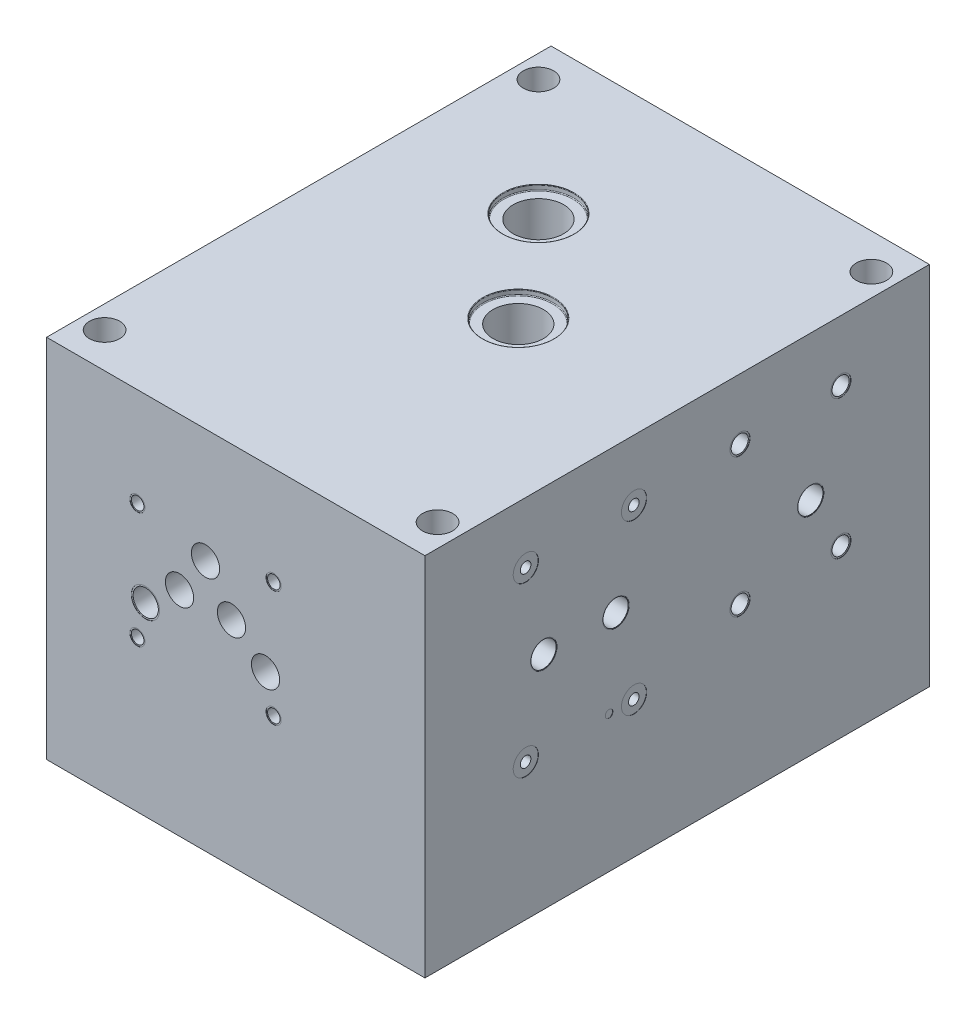
SolidWorks part; units mm, degrees
ref_plane "前视基准面" through (0, 0, 0) normal (0, 0, 1) x (1, 0, 0)
ref_plane "上视基准面" through (0, 0, 0) normal (0, 1, 0) x (1, 0, 0)
ref_plane "右视基准面" through (0, 0, 0) normal (1, 0, 0) x (0, 0, -1)
sketch "草图1" plane through (0, 0, 0) normal (0, 1, 0) x (1, 0, 0)
  line L1 (-75, -100) -> (75, -100)
  line L2 (-75, -100) -> (-75, 100)
  line L3 (-75, 100) -> (75, 100)
  line L4 (75, -100) -> (75, 100)
  line L5 (-75, -100) -> (75, 100) construction
  line L6 (-75, 100) -> (75, -100) construction
  point P0 (0, 0)
  dimension "D1" = 150
  dimension "D2" = 200
extrude "凸台-拉伸1" add sketch "草图1" along normal blind 145
sketch "草图2" plane through (0, 145, 0) normal (0, 1, 0) x (1, 0, 0)
  line L2 (-75, -100) -> (75, -100) construction
  line L3 (-75, 100) -> (-75, -100) construction
  line L4 (75, -100) -> (75, 100) construction
  circle A0 centre (12, 0) radius 10
  circle A1 centre (-20, 40) radius 10
  dimension "D1" = 20
  dimension "D4" = 20
  dimension "D2" = 100
  dimension "D3" = 87
  dimension "D5" = 95
  dimension "D6" = 140
extrude "切除-拉伸1" cut sketch "草图2" against normal through all
sketch "草图4" plane through (0, 0, 100) normal (0, 0, 1) x (1, 0, 0)
  line L0 (0, -7.783) -> (0, 155.8049) construction
  line L1 (-75, 0) -> (75, 0) construction
  line L2 (75, 145) -> (75, 0) construction
  circle A0 centre (15, 60) radius 3
  circle A1 centre (-39, 60) radius 3
  circle A2 centre (-39, 106) radius 3
  circle A3 centre (15, 106) radius 3
  circle A4 centre (-12, 99.7) radius 5.6
  circle A5 centre (-22.3, 84.6) radius 5.6
  circle A6 centre (-35.8, 73.5) radius 5.6
  circle A7 centre (-1.7, 84.6) radius 5.6
  circle A8 centre (11.8, 73.5) radius 5.6
  dimension "D1" = 6
  dimension "D4" = 6
  dimension "D2" = 6
  dimension "D3" = 6
  dimension "D10" = 11.2
  dimension "D13" = 11.2
  dimension "D16" = 11.2
  dimension "D19" = 11.2
  dimension "D22" = 11.2
  dimension "D5" = 54
  dimension "D6" = 46
  dimension "D7" = 54
  dimension "D8" = 60
  dimension "D9" = 60
  dimension "D11" = 27
  dimension "D12" = 6.3
  dimension "D14" = 21.4
  dimension "D15" = 16.7
  dimension "D17" = 3.2
  dimension "D18" = 32.5
  dimension "D20" = 21.4
  dimension "D21" = 37.3
  dimension "D23" = 50.8
  dimension "D24" = 32.5
extrude "切除-拉伸2" cut sketch "草图4" against normal blind 0.1
hole_wizard "M6 螺纹孔1" positions "3D草图1" profile "草图5" tap size "M6" standard "GB"
sketch3d "3D草图1"
  line L0 (-39, 106, 99.9) -> (-39, 106, 100) construction
  line L1 (-39, 60, 99.9) -> (-39, 60, 100) construction
  line L2 (15, 60, 99.9) -> (15, 60, 100) construction
  line L3 (15, 106, 99.9) -> (15, 106, 100) construction
  point P0 (-39, 106, 99.9)
  point P4 (-39, 60, 99.9)
  point P8 (15, 60, 99.9)
  point P12 (15, 106, 100)
sketch "草图5" plane through (-39, 106, 99.9) normal (1, 0, 0) x (0, -1, 0)
  line L0 (0, 0) -> (0, 16.5022)
  line L1 (0, 16.5022) -> (2.5, 15)
  line L2 (2.5, 15) -> (2.5, 0)
  line L5 (2.5, 0) -> (0, 0)
  line L10 (0, 16.5022) -> (-2.5, 15) construction
  line L11 (0, -6.35) -> (0, 107.95) construction
  dimension "螺纹孔钻头直径" = 5
  dimension "螺纹孔钻头深度" = 15
  dimension "导头角度" = 118
cosmetic thread "孔螺蚊线1" parameters "D1"=12, "D2"=6
cosmetic thread "孔螺蚊线2" parameters "D1"=12, "D2"=6
cosmetic thread "孔螺蚊线3" parameters "D1"=12, "D2"=6
cosmetic thread "孔螺蚊线4" parameters "D1"=12, "D2"=6
sketch "草图6" plane through (75, 0, 0) normal (1, 0, 0) x (0, 0, -1)
  line L0 (-100, 145) -> (-100, 0) construction
  line L2 (-100, 0) -> (100, 0) construction
  circle A0 centre (-60, 120.9) radius 5
  circle A1 centre (-17.1, 120.9) radius 5
  circle A2 centre (-60, 54.2) radius 5
  circle A3 centre (-17.1, 54.2) radius 5
  circle A4 centre (52.9, 87.6) radius 5.25
  circle A5 centre (-52.9, 87.6) radius 5.25
  circle A6 centre (-24.3, 87.6) radius 5.25
  circle A7 centre (-27, 54.2) radius 1.5
  circle A8 centre (24.9, 120.9) radius 4
  circle A9 centre (64.9, 120.9) radius 4
  circle A10 centre (24.9, 65.9) radius 4
  circle A11 centre (64.9, 65.9) radius 4
  dimension "D1" = 10
  dimension "D4" = 10
  dimension "D6" = 10
  dimension "D8" = 10
  dimension "D10" = 10.5
  dimension "D13" = 10.5
  dimension "D16" = 10.5
  dimension "D18" = 3
  dimension "D11" = 8
  dimension "D12" = 8
  dimension "D21" = 8
  dimension "D22" = 8
  dimension "D2" = 40
  dimension "D3" = 120.9
  dimension "D5" = 42.9
  dimension "D7" = 66.7
  dimension "D9" = 66.7
  dimension "D14" = 33.3
  dimension "D15" = 7.1
  dimension "D17" = 35.7
  dimension "D19" = 33
  dimension "D20" = 66.7
  dimension "D23" = 42
  dimension "D24" = 55
  dimension "D25" = 40
  dimension "D26" = 33.3
  dimension "D27" = 28
extrude "切除-拉伸3" cut sketch "草图6" against normal blind 0.1
hole_wizard "M5 螺纹孔2" positions "3D草图3" profile "草图8" tap size "M5" standard "GB"
sketch3d "3D草图3"
  line L0 (74.9, 120.9, 60) -> (75, 120.9, 60) construction
  line L1 (74.9, 120.9, 17.1) -> (75, 120.9, 17.1) construction
  line L2 (74.9, 54.2, 17.1) -> (75, 54.2, 17.1) construction
  line L3 (74.9, 54.2, 60) -> (75, 54.2, 60) construction
  point P0 (74.9, 120.9, 60)
  point P4 (74.9, 120.9, 17.1)
  point P8 (75, 54.2, 17.1)
  point P12 (74.9, 54.2, 60)
sketch "草图8" plane through (74.9, 120.9, 60) normal (0, 1, 0) x (0, 0, -1)
  line L0 (0, 0) -> (0, 13.6618)
  line L1 (0, 13.6618) -> (2.1, 12.4)
  line L2 (2.1, 12.4) -> (2.1, 0)
  line L5 (2.1, 0) -> (0, 0)
  line L10 (0, 13.6618) -> (-2.1, 12.4) construction
  line L11 (0, -6.35) -> (0, 107.95) construction
  dimension "螺纹孔钻头直径" = 4.2
  dimension "螺纹孔钻头深度" = 12.4
  dimension "导头角度" = 118
cosmetic thread "孔螺蚊线5" parameters "D1"=10, "D2"=5
cosmetic thread "孔螺蚊线6" parameters "D1"=10, "D2"=5
cosmetic thread "孔螺蚊线7" parameters "D1"=10, "D2"=5
cosmetic thread "孔螺蚊线8" parameters "D1"=10, "D2"=5
hole_wizard "Ø11.2 (11.2) 直径孔1" positions "3D草图4" profile "草图10" hole size "Ø11.2" standard "GB"
sketch3d "3D草图4"
  line L0 (-12, 99.7, 99.9) -> (-12, 99.7, 100) construction
  point P0 (-12, 99.7, 100)
sketch "草图10" plane through (-12, 99.7, 100) normal (1, 0, 0) x (0, -1, 0)
  line L0 (0, 0) -> (0, 83.3648)
  line L1 (0, 83.3648) -> (5.6, 80)
  line L2 (5.6, 80) -> (5.6, 0)
  line L5 (5.6, 0) -> (0, 0)
  line L10 (0, 83.3648) -> (-5.6, 80) construction
  line L11 (0, -6.35) -> (0, 107.95) construction
  dimension "孔直径" = 11.2
  dimension "孔深度" = 80
  dimension "导头角度" = 118
hole_wizard "Ø11.2 (11.2) 直径孔2" positions "3D草图5" profile "草图12" hole size "Ø11.2" standard "GB"
sketch3d "3D草图5"
  line L0 (11.8, 73.5, 99.9) -> (11.8, 73.5, 100) construction
  point P0 (11.8, 73.5, 99.9)
sketch "草图12" plane through (11.8, 73.5, 99.9) normal (1, 0, 0) x (0, -1, 0)
  line L0 (0, 0) -> (0, 58.3648)
  line L1 (0, 58.3648) -> (5.6, 55)
  line L2 (5.6, 55) -> (5.6, 0)
  line L5 (5.6, 0) -> (0, 0)
  line L10 (0, 58.3648) -> (-5.6, 55) construction
  line L11 (0, -6.35) -> (0, 107.95) construction
  dimension "孔直径" = 11.2
  dimension "孔深度" = 55
  dimension "导头角度" = 118
hole_wizard "Ø11.2 (11.2) 直径孔3" positions "3D草图7" profile "草图14" hole size "Ø11.2" standard "GB"
sketch3d "3D草图7"
  line L0 (-1.7, 84.6, 99.9) -> (-1.7, 84.6, 100) construction
  point P0 (-1.7, 84.6, 99.9)
sketch "草图14" plane through (-1.7, 84.6, 99.9) normal (1, 0, 0) x (0, -1, 0)
  line L0 (0, 0) -> (0, 58.3648)
  line L1 (0, 58.3648) -> (5.6, 55)
  line L2 (5.6, 55) -> (5.6, 0)
  line L5 (5.6, 0) -> (0, 0)
  line L10 (0, 58.3648) -> (-5.6, 55) construction
  line L11 (0, -6.35) -> (0, 107.95) construction
  dimension "孔直径" = 11.2
  dimension "孔深度" = 55
  dimension "导头角度" = 118
hole_wizard "Ø10.0 (10) 直径孔2" positions "3D草图10" profile "草图22" hole size "Ø10.0" standard "GB"
sketch3d "3D草图10"
  line L0 (-35.8, 73.5, 99.9) -> (-35.8, 73.5, 100) construction
  point P0 (-35.8, 73.5, 100)
sketch "草图22" plane through (-35.8, 73.5, 100) normal (1, 0, 0) x (0, -1, 0)
  line L0 (0, 0) -> (0, 143.0043)
  line L1 (0, 143.0043) -> (5, 140)
  line L2 (5, 140) -> (5, 0)
  line L5 (5, 0) -> (0, 0)
  line L10 (0, 143.0043) -> (-5, 140) construction
  line L11 (0, -6.35) -> (0, 107.95) construction
  dimension "孔直径" = 10
  dimension "孔深度" = 140
  dimension "导头角度" = 118
hole_wizard "Ø11.2 (11.2) 直径孔5" positions "3D草图11" profile "草图23" hole size "Ø11.2" standard "GB"
sketch3d "3D草图11"
  line L0 (-22.3, 84.6, 99.9) -> (-22.3, 84.6, 100) construction
  point P0 (-22.3, 84.6, 100)
sketch "草图23" plane through (-22.3, 84.6, 100) normal (1, 0, 0) x (0, -1, 0)
  line L0 (0, 0) -> (0, 58.3648)
  line L1 (0, 58.3648) -> (5.6, 55)
  line L2 (5.6, 55) -> (5.6, 0)
  line L5 (5.6, 0) -> (0, 0)
  line L10 (0, 58.3648) -> (-5.6, 55) construction
  line L11 (0, -6.35) -> (0, 107.95) construction
  dimension "孔直径" = 11.2
  dimension "孔深度" = 55
  dimension "导头角度" = 118
sketch "草图25" plane through (-75, 0, 0) normal (-1, 0, 0) x (0, 0, 1)
  line L0 (-100, 145) -> (100, 145) construction
  line L1 (100, 145) -> (100, 0) construction
  circle A0 centre (52, 89) radius 6
  dimension "D2" = 12
  dimension "D1" = 56
  dimension "D3" = 48
extrude "切除-拉伸13" cut sketch "草图25" against normal blind 0.1
cosmetic thread "装饰螺纹线10" parameters "D1"=6, "D2"=12.1
hole_wizard "Ø12.0 (12) 直径孔1" positions "3D草图12" profile "草图26" hole size "Ø12.0" standard "GB"
sketch3d "3D草图12"
  line L0 (-74.9, 89, 52) -> (-75, 89, 52) construction
  point P0 (-74.9, 89, 52)
sketch "草图26" plane through (-74.9, 89, 52) normal (0, 1, 0) x (0, 0, 1)
  line L0 (0, 0) -> (0, 55.6052)
  line L1 (0, 55.6052) -> (6, 52)
  line L2 (6, 52) -> (6, 0)
  line L5 (6, 0) -> (0, 0)
  line L10 (0, 55.6052) -> (-6, 52) construction
  line L11 (0, -6.35) -> (0, 107.95) construction
  dimension "孔直径" = 12
  dimension "孔深度" = 52
  dimension "导头角度" = 118
sketch "草图27" plane through (0, 0, -100) normal (0, 0, -1) x (-1, 0, 0)
  line L0 (-75, 145) -> (75, 145) construction
  line L1 (75, 145) -> (75, 0) construction
  circle A0 centre (40, 88) radius 13.5
  dimension "D2" = 27
  dimension "D1" = 57
  dimension "D3" = 35
extrude "切除-拉伸14" cut sketch "草图27" against normal blind 18
cosmetic thread "装饰螺纹线8" parameters "D1"=16, "D2"=27.1
sketch "草图31" plane through (0, 0, 0) normal (0, -1, 0) x (1, 0, 0)
  line L3 (-75, 100) -> (75, 100) construction
  line L4 (-75, -100) -> (-75, 100) construction
  circle A0 centre (-20, 19.3) radius 7
  dimension "D1" = 14
  dimension "D3" = 55
  dimension "D2" = 80.7
extrude "切除-拉伸16" cut sketch "草图31" against normal blind 1
sketch "草图34" plane through (-75, 0, 0) normal (-1, 0, 0) x (0, 0, 1)
  line L0 (100, 145) -> (100, 0) construction
  line L1 (-100, 145) -> (100, 145) construction
  circle A0 centre (52, 67.5) radius 6
  dimension "D3" = 12
  dimension "D1" = 48
  dimension "D2" = 77.5
extrude "切除-拉伸18" cut sketch "草图34" against normal blind 0.1
cosmetic thread "装饰螺纹线11" parameters "D1"=6, "D2"=12.1
hole_wizard "Ø14.75 (14.75) 直径孔1" positions "3D草图26" profile "草图60" hole size "Ø14.75" standard "GB"
sketch3d "3D草图26"
  line L0 (-20, 1, 19.3) -> (-20, 0, 19.3) construction
  point P0 (-20, 0, 19.3)
sketch "草图60" plane through (-20, 0, 19.3) normal (1, 0, 0) x (0, 0, -1)
  line L0 (0, 0) -> (0, 112.4313)
  line L1 (0, 112.4313) -> (7.375, 108)
  line L2 (7.375, 108) -> (7.375, 0)
  line L5 (7.375, 0) -> (0, 0)
  line L10 (0, 112.4313) -> (-7.375, 108) construction
  line L11 (0, -6.35) -> (0, 107.95) construction
  dimension "孔直径" = 14.75
  dimension "孔深度" = 108
  dimension "导头角度" = 118
hole_wizard "Ø12.0 (12) 直径孔2" positions "3D草图13" profile "草图35" hole size "Ø12.0" standard "GB"
sketch3d "3D草图13"
  line L0 (-74.9, 67.5, 52) -> (-75, 67.5, 52) construction
  point P0 (-75, 67.5, 52)
sketch "草图35" plane through (-75, 67.5, 52) normal (0, 1, 0) x (0, 0, 1)
  line L0 (0, 0) -> (0, 88.6052)
  line L1 (0, 88.6052) -> (6, 85)
  line L2 (6, 85) -> (6, 0)
  line L5 (6, 0) -> (0, 0)
  line L10 (0, 88.6052) -> (-6, 85) construction
  line L11 (0, -6.35) -> (0, 107.95) construction
  dimension "孔直径" = 12
  dimension "孔深度" = 85
  dimension "导头角度" = 118
hole_wizard "Ø10.0 (10) 直径孔5" positions "3D草图14" profile "草图37" hole size "Ø10.0" standard "GB"
sketch3d "3D草图14"
  line L0 (74.9, 87.6, 52.9) -> (75, 87.6, 52.9) construction
  point P0 (75, 87.6, 52.9)
sketch "草图37" plane through (75, 87.6, 52.9) normal (0, 1, 0) x (0, 0, -1)
  line L0 (0, 0) -> (0, 79.0043)
  line L1 (0, 79.0043) -> (5, 76)
  line L2 (5, 76) -> (5, 0)
  line L5 (5, 0) -> (0, 0)
  line L10 (0, 79.0043) -> (-5, 76) construction
  line L11 (0, -6.35) -> (0, 107.95) construction
  dimension "孔直径" = 10
  dimension "孔深度" = 76
  dimension "导头角度" = 118
sketch "草图42" plane through (-75, 0, 0) normal (-1, 0, 0) x (0, 0, 1)
  line L0 (-100, 145) -> (100, 145) construction
  line L1 (-100, 145) -> (-100, 0) construction
  circle A0 centre (-38, 73.5) radius 6
  dimension "D3" = 12
  dimension "D1" = 71.5
  dimension "D2" = 62
extrude "切除-拉伸19" cut sketch "草图42" against normal blind 50
cosmetic thread "装饰螺纹线9" parameters "D1"=6, "D2"=12.1
hole_wizard "M8 螺纹孔1" positions "3D草图15" profile "草图44" tap size "M8" standard "GB"
sketch3d "3D草图15"
  line L0 (74.9, 120.9, -24.9) -> (75, 120.9, -24.9) construction
  line L1 (74.9, 65.9, -24.9) -> (75, 65.9, -24.9) construction
  line L2 (74.9, 65.9, -64.9) -> (75, 65.9, -64.9) construction
  line L3 (74.9, 120.9, -64.9) -> (75, 120.9, -64.9) construction
  point P0 (74.9, 120.9, -24.9)
  point P4 (74.9, 65.9, -24.9)
  point P8 (74.9, 65.9, -64.9)
  point P12 (75, 120.9, -64.9)
sketch "草图44" plane through (74.9, 120.9, -24.9) normal (0, 1, 0) x (0, 0, -1)
  line L0 (0, 0) -> (0, 21.7929)
  line L1 (0, 21.7929) -> (3.4, 19.75)
  line L2 (3.4, 19.75) -> (3.4, 0)
  line L5 (3.4, 0) -> (0, 0)
  line L10 (0, 21.7929) -> (-3.4, 19.75) construction
  line L11 (0, -6.35) -> (0, 107.95) construction
  dimension "螺纹孔钻头直径" = 6.8
  dimension "螺纹孔钻头深度" = 19.75
  dimension "导头角度" = 118
cosmetic thread "孔螺蚊线9" parameters "D1"=16, "D2"=8
cosmetic thread "孔螺蚊线10" parameters "D1"=16, "D2"=8
cosmetic thread "孔螺蚊线11" parameters "D1"=16, "D2"=8
cosmetic thread "孔螺蚊线12" parameters "D1"=16, "D2"=8
hole_wizard "Ø10.0 (10) 直径孔6" positions "3D草图16" profile "草图45" hole size "Ø10.0" standard "GB"
sketch3d "3D草图16"
  line L0 (74.9, 87.6, -52.9) -> (75, 87.6, -52.9) construction
  point P0 (75, 87.6, -52.9)
sketch "草图45" plane through (75, 87.6, -52.9) normal (0, 1, 0) x (0, 0, -1)
  line L0 (0, 0) -> (0, 51.0043)
  line L1 (0, 51.0043) -> (5, 48)
  line L2 (5, 48) -> (5, 0)
  line L5 (5, 0) -> (0, 0)
  line L10 (0, 51.0043) -> (-5, 48) construction
  line L11 (0, -6.35) -> (0, 107.95) construction
  dimension "孔直径" = 10
  dimension "孔深度" = 48
  dimension "导头角度" = 118
hole_wizard "Ø10.0 (10) 直径孔7" positions "草图46" profile "草图47" hole size "Ø10.0" standard "GB"
sketch "草图46" plane through (75, 0, 0) normal (1, 0, 0) x (0, 0, -1)
  point P0 (-24.3, 87.6)
sketch "草图47" plane through (75, 87.6, 24.3) normal (0, 1, 0) x (0, 0, -1)
  line L0 (0, 0) -> (0, 51.0043)
  line L1 (0, 51.0043) -> (5, 48)
  line L2 (5, 48) -> (5, 0)
  line L5 (5, 0) -> (0, 0)
  line L10 (0, 51.0043) -> (-5, 48) construction
  line L11 (0, -6.35) -> (0, 107.95) construction
  dimension "孔直径" = 10
  dimension "孔深度" = 48
  dimension "导头角度" = 118
sketch "草图48" plane through (0, 0, -100) normal (0, 0, -1) x (-1, 0, 0)
  line L0 (-75, 145) -> (-75, 0) construction
  line L1 (-75, 0) -> (75, 0) construction
  circle A0 centre (-35, 87.6) radius 13.5
  dimension "D3" = 27
  dimension "D1" = 40
  dimension "D2" = 87.6
extrude "切除-拉伸20" cut sketch "草图48" against normal blind 18
cosmetic thread "装饰螺纹线7" parameters "D1"=16, "D2"=27.1
hole_wizard "Ø10.0 (10) 直径孔9" positions "3D草图22" profile "草图54" hole size "Ø10.0" standard "GB"
sketch3d "3D草图22"
  line L0 (35, 87.6, -82) -> (35, 87.6, -100) construction
  point P0 (35, 87.6, -82)
sketch "草图54" plane through (35, 87.6, -82) normal (1, 0, 0) x (0, 1, 0)
  line L0 (0, 0) -> (0, 118.0043)
  line L1 (0, 118.0043) -> (5, 115)
  line L2 (5, 115) -> (5, 0)
  line L5 (5, 0) -> (0, 0)
  line L10 (0, 118.0043) -> (-5, 115) construction
  line L11 (0, -6.35) -> (0, 107.95) construction
  dimension "孔直径" = 10
  dimension "孔深度" = 115
  dimension "导头角度" = 118
sketch "草图55" plane through (0, 0, -82) normal (0, 0, -1) x (-1, 0, 0)
  circle A0 centre (40, 88) radius 5
  dimension "D1" = 10
extrude "切除-拉伸21" cut sketch "草图55" against normal up to next
sketch "草图58" plane through (0, 145, 0) normal (0, 1, 0) x (1, 0, 0)
  circle A0 centre (12, 0) radius 14
  circle A1 centre (-20, 40) radius 14
  dimension "D1" = 28
  dimension "D2" = 28
extrude "切除-拉伸23" cut sketch "草图58" against normal blind 1.97
sketch "草图59" plane through (-75, 0, 0) normal (-1, 0, 0) x (0, 0, 1)
  circle A0 centre (52, 67.5) radius 9
  circle A1 centre (52, 89) radius 9
  circle A2 centre (-38, 73.5) radius 8.5
  dimension "D1" = 18
  dimension "D2" = 18
  dimension "D3" = 17
extrude "切除-拉伸24" cut sketch "草图59" against normal blind 8
fillet "圆角1" radius 0.3 2 edges at (-20, 143.03, -26) (12, 143.03, 14)
fillet "圆角2" radius 0.2 2 edges at (-20, 145, -26) (12, 145, 14)
sketch "草图62" plane through (0, 145, 0) normal (0, 1, 0) x (1, 0, 0)
  line L0 (-75, 100) -> (-75, -100) construction
  line L1 (75, 100) -> (-75, 100) construction
  line L2 (-105.7934, 0) -> (128.4309, 0) construction
  line L3 (0, -113.3944) -> (0, 128.5346) construction
  line L4 (-60, 86) -> (-55.5404, 86)
  circle A0 centre (-66, 86) radius 6
  circle A1 centre (-66, -86) radius 6
  circle A2 centre (66, 86) radius 6
  circle A3 centre (66, -86) radius 6
  dimension "D1" = 12
  dimension "D2" = 9
  dimension "D3" = 14
extrude "切除-拉伸25" cut sketch "草图62" against normal through all contours A2 | A0 | A1 | A3 region at (66, 145, -86)
